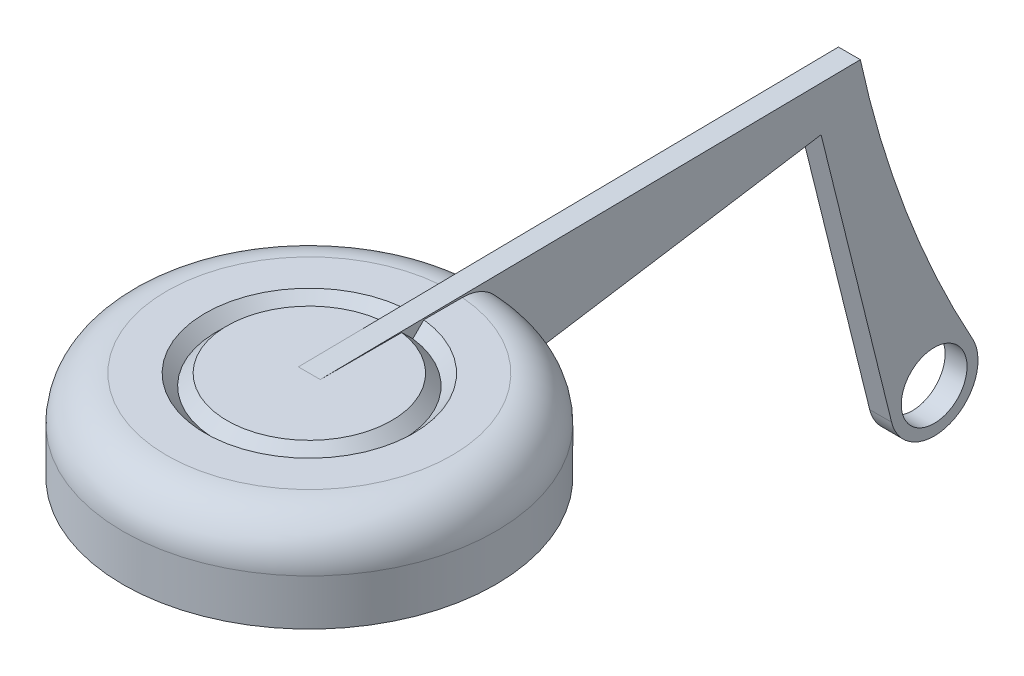
SolidWorks part; units mm, degrees
ref_plane "Front Plane" through (0, 0, 0) normal (0, 0, 1) x (1, 0, 0)
ref_plane "Top Plane" through (0, 0, 0) normal (0, 1, 0) x (1, 0, 0)
ref_plane "Right Plane" through (0, 0, 0) normal (1, 0, 0) x (0, 0, -1)
sketch "Sketch4" plane through (0, 0, 0) normal (1, 0, 0) x (0, 0, -1)
  line L0 (0, 0) -> (-3.75, 0)
  line L1 (-3.75, 0) -> (-4.25, -0.5)
  line L2 (-4.25, -0.5) -> (-4.75, 0)
  line L3 (-4.75, 0) -> (-8.5, 0)
  line L4 (-8.5, 0) -> (-8.5, -4)
  line L5 (-8.5, -4) -> (0, -4)
  line L6 (0, 0) -> (0, -4)
  line L7 (-8.5, -0.5) -> (0, -0.5) construction
  line L8 (0, 1.8905) -> (0, -6.6755) construction
  point P3 (-4.25, -0.5)
  dimension "D1" = 8.5
  dimension "D2" = 0.5
  dimension "D3" = 4
revolve "Revolve1" add sketch "Sketch4" angle 360 about L8
fillet "Fillet1" radius 2 1 edges at (0, 0, 8.5)
sketch "Sketch5" plane through (0, -4, 0) normal (0, -1, 0) x (1, 0, 0)
  circle A0 centre (0, 0) radius 8.5
  circle A1 centre (0, 0) radius 7
  dimension "D1" = 14
extrude "Boss-Extrude1" add sketch "Sketch5" along normal blind 0.1 separate body
sketch "Sketch6" plane through (0, 0, 0) normal (1, 0, 0) x (0, 0, -1)
  line L0 (0, 0) -> (24.6329, 0.32)
  line L1 (8.5, -4) -> (22.8424, -1.7485)
  line L2 (8.5, -4) -> (8.5, -2) construction
  line L3 (8.5, -4) -> (-8.5, -4) construction
  line L4 (22.8424, -1.7485) -> (26.0588, -14.7165)
  line L5 (0, 0) -> (0, -0.9077)
  line L6 (0, -0.9077) -> (7.1744, -0.9077)
  line L7 (7.1744, -0.9077) -> (8.5, -4)
  circle A0 centre (28, -14.235) radius 1.5
  circle A1 centre (28, -14.235) radius 2
  arc A2 (24.6329, 0.32) -> (29.7496, -13.266) centre (73.507, 10.9702) ccw
  point P5 (28, -4)
  point P6 (28, -6.747)
  point P17 (23.2395, -4)
  point P21 (28, -11.262)
  point P22 (24.8424, -1.7485)
  point P23 (8.5, -4)
  point P24 (28, -16.559)
  point P25 (28, -14.235)
  dimension "D1" = 3
  dimension "D2" = 4
  dimension "D3" = 28
extrude "Boss-Extrude2" add sketch "Sketch6" along normal blind 0.5 and the other way blind 0.5 contours A2 L0 L5 L6 L7 L1 L4 A1 | A1 A0 region at (0, -0.1733, -12.3208) region at (0, -13.7487, -29.8816)
